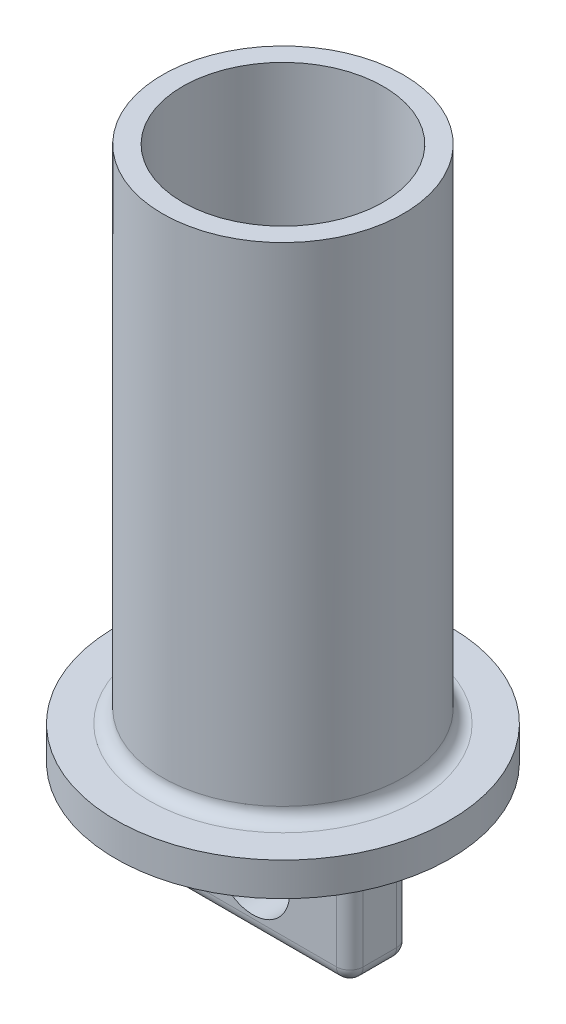
SolidWorks part; units mm, degrees
ref_plane "Front Plane" through (0, 0, 0) normal (0, 0, 1) x (1, 0, 0)
ref_plane "Top Plane" through (0, 0, 0) normal (0, 1, 0) x (1, 0, 0)
ref_plane "Right Plane" through (0, 0, 0) normal (1, 0, 0) x (0, 0, -1)
sketch "Sketch1" plane through (0, 0, 0) normal (0, 1, 0) x (1, 0, 0)
  line L2 (3.8823, 14.4889) -> (3.3646, 12.557)
  line L3 (14.4889, 3.8823) -> (12.557, 3.3646)
  line L4 (-3.3646, -12.557) -> (-3.8823, -14.4889)
  line L5 (3.8823, -14.4889) -> (3.3646, -12.557)
  line L6 (-14.4889, 3.8823) -> (-12.557, 3.3646)
  line L7 (-3.3646, 12.557) -> (-3.8823, 14.4889)
  line L8 (12.557, -3.3646) -> (14.4889, -3.8823)
  line L10 (-12.557, -3.3646) -> (-14.4889, -3.8823)
  circle A0 centre (0, 0) radius 13
  circle A2 centre (0, 0) radius 15
  circle A3 centre (0, 0) radius 18
extrude "Boss-Extrude1" add sketch "Sketch1" along normal blind 80 contours A3 A2 region at (-17.4909, 0, 0)
extrude "Boss-Extrude2" add sketch "Sketch1<3>" along normal blind 5 contours L3 A2 L2 A0 | L8 A2 L3 A0 | L5 A2 L8 A0 | L4 A2 L5 A0 | L10 A2 L4 A0 | L6 A2 L10 A0 | L7 A2 L6 A0 | L2 A2 L7 A0 region at (9.4694, 0, -9.4694) region at (0, 0, -13.8642) region at (13.8642, 0, 0) region at (-9.4694, 0, -9.4694) region at (-13.8642, 0, 0) region at (9.4694, 0, 9.4694) region at (-9.4694, 0, 9.4694) region at (0, 0, 13.8642)
sketch "Sketch1<3>" plane through (0, 0, 0) normal (0, 1, 0) x (1, 0, 0) same geometry as "Sketch1"
extrude "Boss-Extrude4" add sketch "Sketch1<4>" along normal blind 10 contours L6 A2 L10 | L2 A2 L7 | L4 A2 L5 | L8 A2 L3 region at (0, 0, -13.8642) region at (13.8642, 0, 0) region at (-13.8642, 0, 0) region at (0, 0, 13.8642)
sketch "Sketch1<4>" plane through (0, 0, 0) normal (0, 1, 0) x (1, 0, 0) same geometry as "Sketch1"
sketch3d "3DSketch3" plane through (0, 0, 0) normal (0, 0, 1) x (1, 0, 0)
  dimension "D1" = 2.5
sketch "Sketch3" plane through (0, 0, 0) normal (0, -1, 0) x (1, 0, 0)
  circle A0 centre (0, 0) radius 20
  circle A1 centre (0, 0) radius 25
  circle A2 centre (0, 0) radius 18
  circle M1 centre (0, 0) radius 13
  circle M2 centre (0, 0) radius 18
extrude "Boss-Extrude6" add sketch "Sketch3" against normal blind 5 contours A0 M2 | A1 A0 | M1 region at (-19.4343, 0, 0) region at (-24.2929, 0, 0) region at (0, 0, 0)
sketch "Sketch15" plane through (0, 0, 0) normal (0, -1, 0) x (1, 0, 0)
  line L1 (-14.5, -4.5) -> (14.5, -4.5)
  line L2 (-14.5, -4.5) -> (-14.5, 4.5)
  line L3 (-14.5, 4.5) -> (14.5, 4.5)
  line L4 (14.5, -4.5) -> (14.5, 4.5)
  line L5 (-14.5, -4.5) -> (14.5, 4.5) construction
  line L6 (-14.5, 4.5) -> (14.5, -4.5) construction
  point P0 (0, 0)
extrude "Boss-Extrude13" add sketch "Sketch15" along normal blind 20
sketch "Sketch16" plane through (0, 0, 4.5) normal (0, 0, 1) x (1, 0, 0)
  circle A0 centre (0, -12) radius 5.5
extrude "Cut-Extrude3" cut sketch "Sketch16" against normal through all
fillet "Fillet1" radius 2 13 edges at (0, 0, 4.5) (-14.5, 0, 0) (-14.5, -20, 0) (14.5, -20, 0) (0, -20, -4.5) (0, -20, 4.5) (14.5, -10, 4.5) (-14.5, -10, 4.5) (-14.5, -10, -4.5) (14.5, -10, -4.5) (0, 0, -4.5) (14.5, 0, 0) (0, 5, -18)
sketch "Sketch17" plane through (0, 0, 4.5) normal (0, 0, 1) x (1, 0, 0)
  point P0 (0, -12)
sketch "Sketch18" plane through (0, 0, -4.5) normal (0, 0, -1) x (-1, 0, 0)
  point P0 (0, -12)
